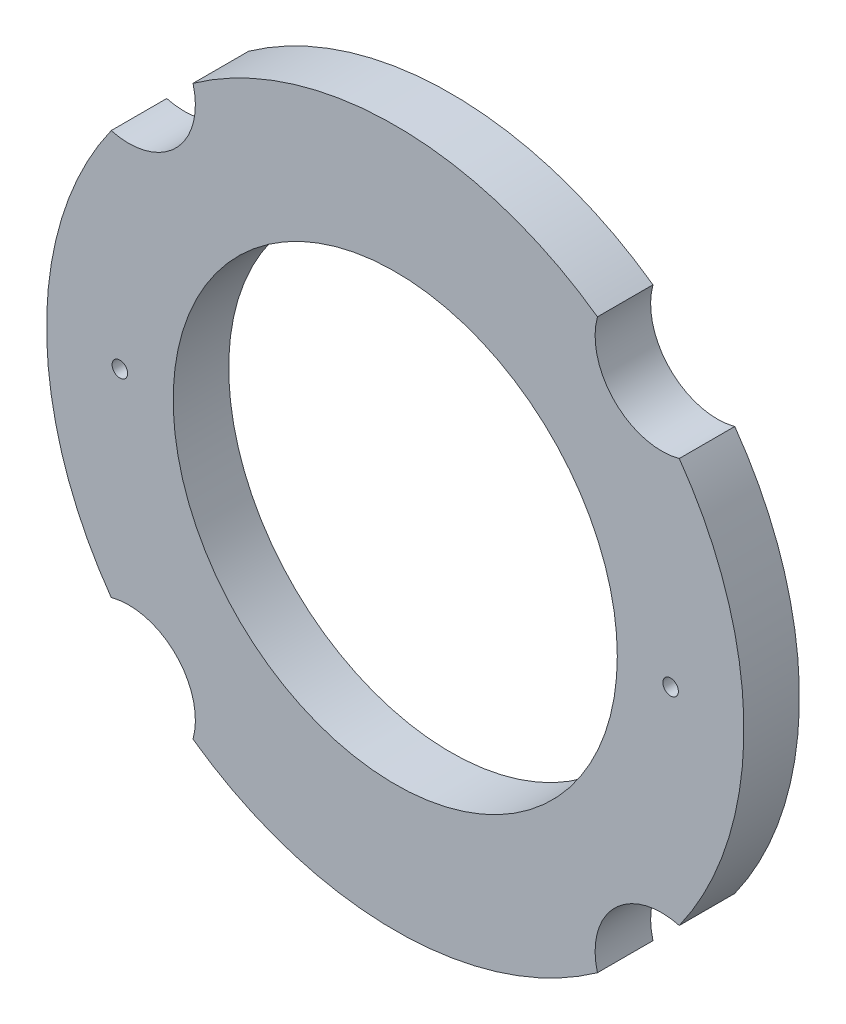
SolidWorks part; units mm, degrees
ref_plane "前视基准面" through (0, 0, 0) normal (0, 0, 1) x (1, 0, 0)
ref_plane "上视基准面" through (0, 0, 0) normal (0, 1, 0) x (1, 0, 0)
ref_plane "右视基准面" through (0, 0, 0) normal (1, 0, 0) x (0, 0, -1)
sketch "草图1" plane through (0, 0, 0) normal (0, 0, 1) x (1, 0, 0)
  line L0 (0, 0) -> (-62, 0)
  line L1 (0, 0) -> (0, 18.0408)
  circle A0 centre (0, 0) radius 50
  circle A1 centre (0, 0) radius 78.5
  circle A2 centre (-62, 0) radius 5
  circle A3 centre (62, 0) radius 5
  circle A4 centre (-62, 0) radius 1.75
  circle A5 centre (62, 0) radius 1.75
  circle A6 centre (-60, 60) radius 15
  circle A7 centre (60, 60) radius 15
  circle A8 centre (60, -60) radius 15
  circle A9 centre (-60, -60) radius 15
  point P25 (0, 0)
  dimension "D1" = 100
  dimension "D2" = 157
  dimension "D4" = 10
  dimension "D5" = 3.5
  dimension "D6" = 3.5
  dimension "D8" = 30
  dimension "D3" = 62
  dimension "D9" = 4
extrude "凸台-拉伸1" add sketch "草图1" along normal blind 12.5 contours A1 A2 A0 A3 | A3 | A2 region at (-66.8586, 0, 0) region at (72.6587, -23.223, 0) region at (57.1414, 0, 0)
extrude "切除-拉伸1" cut sketch "草图1<3>" along normal blind 4 contours A2 | A3 region at (-66.8586, 0, 0) region at (57.1414, 0, 0)
sketch "草图1<3>" plane through (0, 0, 0) normal (0, 0, 1) x (1, 0, 0) same geometry as "草图1"
